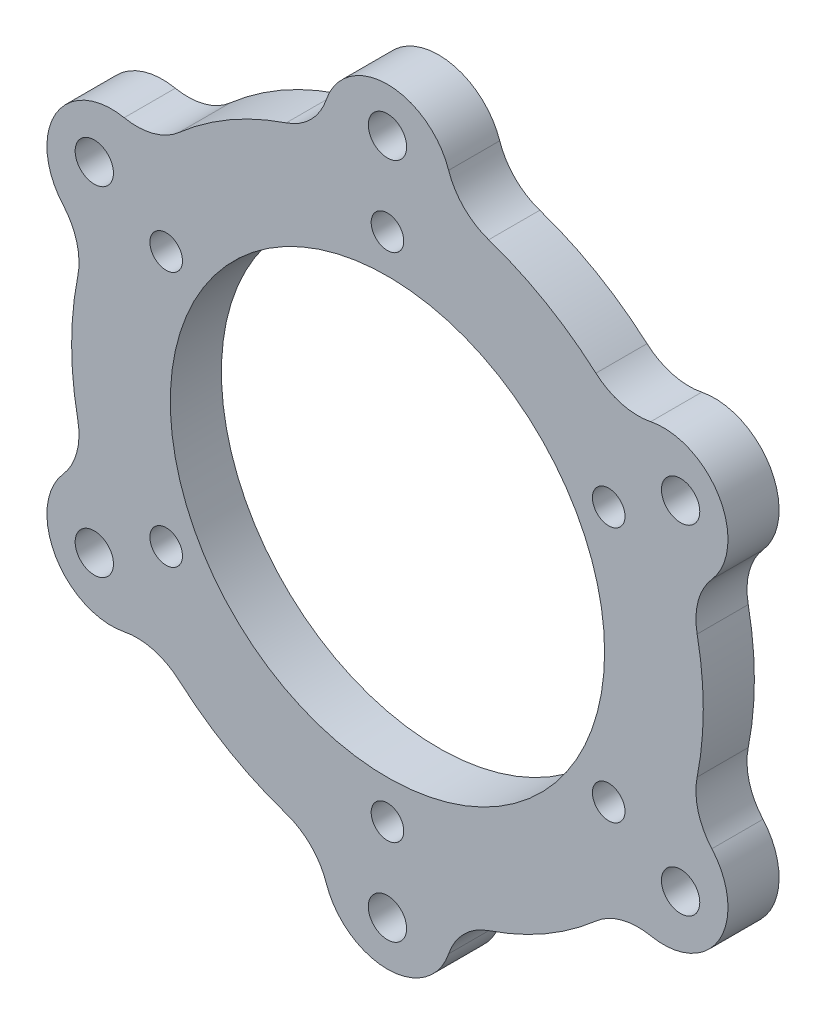
SolidWorks part; units mm, degrees
material "6063-T6"
ref_plane "Front Plane" through (0, 0, 0) normal (0, 0, 1) x (1, 0, 0)
ref_plane "Top Plane" through (0, 0, 0) normal (0, 1, 0) x (1, 0, 0)
ref_plane "Right Plane" through (0, 0, 0) normal (1, 0, 0) x (0, 0, -1)
sketch "Sketch5" plane through (0, 0, 0) normal (0, 1, 0) x (1, 0, 0)
  line L0 (0, -16.5008) -> (0, 15.0181) construction
ref_plane "Plane1" through (0, 0, 0) normal (-0.5, 0.866, 0) x (0, 0, -1)
sketch "Sketch2" plane through (0, 0, 0) normal (0, 0, 1) x (1, 0, 0)
  line L0 (0, 0) -> (0, 53) construction
  line L1 (0, 0) -> (0, 40) construction
  line L2 (0, 0) -> (0, 53) construction
  circle A0 centre (0, 0) radius 34
  circle A1 centre (0, 0) radius 60
  circle A2 centre (0, 53) radius 3
  circle A3 centre (45.8993, 26.5) radius 3
  circle A4 centre (45.8993, -26.5) radius 3
  circle A5 centre (0, -53) radius 3
  circle A6 centre (-45.8993, -26.5) radius 3
  circle A7 centre (-45.8993, 26.5) radius 3
  circle A11 centre (0, 0) radius 53 construction
  circle A12 centre (0, 40) radius 2.55
  circle A13 centre (34.641, 20) radius 2.55
  circle A14 centre (34.641, -20) radius 2.55
  circle A15 centre (0, -40) radius 2.55
  circle A16 centre (-34.641, -20) radius 2.55
  circle A17 centre (-34.641, 20) radius 2.55
  circle A18 centre (0, 0) radius 46.95 construction
  arc A19 (-15.849, 46.8413) -> (15.849, 46.8413) centre (0, 0) ccw
  arc A21 (-9.5776, 53.1206) -> (9.5776, 53.1206) centre (0, 49.8933) cw
  arc A22 (9.5776, 53.1206) -> (15.849, 46.8413) centre (19.0541, 56.3138) ccw
  circle A23 centre (0, 0) radius 49.45 construction
  arc A24 (-9.5776, 53.1206) -> (-15.849, 46.8413) centre (-19.0541, 56.3138) cw
  arc A25 (41.215, 34.8547) -> (50.7926, 18.2658) centre (43.2088, 24.9466) cw
  arc A26 (41.215, 34.8547) -> (32.6413, 37.1463) centre (39.2422, 44.6582) cw
  arc A27 (50.7926, 18.2658) -> (48.4903, 9.695) centre (58.2962, 11.6556) ccw
  arc A28 (50.7926, -18.2658) -> (41.215, -34.8547) centre (43.2088, -24.9466) cw
  arc A29 (50.7926, -18.2658) -> (48.4903, -9.695) centre (58.2962, -11.6556) cw
  arc A30 (41.215, -34.8547) -> (32.6413, -37.1463) centre (39.2422, -44.6582) ccw
  arc A31 (9.5776, -53.1206) -> (-9.5776, -53.1206) centre (0, -49.8933) cw
  arc A32 (9.5776, -53.1206) -> (15.849, -46.8413) centre (19.0541, -56.3138) cw
  arc A33 (-9.5776, -53.1206) -> (-15.849, -46.8413) centre (-19.0541, -56.3138) ccw
  arc A34 (-41.215, -34.8547) -> (-50.7926, -18.2658) centre (-43.2088, -24.9466) cw
  arc A35 (-41.215, -34.8547) -> (-32.6413, -37.1463) centre (-39.2422, -44.6582) cw
  arc A36 (-50.7926, -18.2658) -> (-48.4903, -9.695) centre (-58.2962, -11.6556) ccw
  arc A37 (-50.7926, 18.2658) -> (-41.215, 34.8547) centre (-43.2088, 24.9466) cw
  arc A38 (-50.7926, 18.2658) -> (-48.4903, 9.695) centre (-58.2962, 11.6556) cw
  arc A39 (-41.215, 34.8547) -> (-32.6413, 37.1463) centre (-39.2422, 44.6582) ccw
  point P24 (0, 0)
  point P42 (46.95, 0)
  point P43 (0, 0)
  point P46 (10, 48.4283)
  point P49 (-10, 48.4283)
  point P84 (0, 0)
  dimension "D1" = 6
  dimension "D2" = 68
  dimension "D3" = 120
  dimension "D9" = 5.1
  dimension "D7" = 93.9
  dimension "D12" = 10
  dimension "D10" = 40
  dimension "D4" = 0
  dimension "D11" = 20
  dimension "D8" = 2.5
  dimension "D5" = 6
  dimension "D6" = 6
  dimension "D13" = 6
extrude "Boss-Extrude1" add sketch "Sketch2" along normal blind 8 contours A21 A24 A19 A22 A0 A2 A12 A13 A14 A15 A16 A17 | A39 A37 A38 A19 A7 | A27 A25 A26 A19 A3 | A33 A31 A32 A19 A5 | A36 A34 A35 A19 A6 | A30 A28 A29 A19 A4 region at (52.9238, 23.9788, 0) region at (47.2282, -33.844, 0) region at (5.0355, 56.9038, 0) region at (-5.6959, -57.8232, 0) region at (-47.2282, 33.844, 0) region at (-52.9238, -23.9788, 0)
sketch "Sketch4" plane through (0, 0, 0) normal (-0.5, 0.866, 0) x (0, 0, -1)
  line L0 (0, 0) -> (-8, 0) construction
  line L3 (-16.5008, 0) -> (15.0181, 0) construction
  line L7 (0, -9.695) -> (0, 9.695)
  line L8 (0, 9.695) -> (-8, 9.695)
  line L9 (-8, 9.695) -> (-8, -9.695)
  line L10 (-8, -9.695) -> (0, -9.695)
  line L11 (0, -9.695) -> (0, 9.695)
  line L12 (0, 9.695) -> (-8, 9.695)
  line L13 (-8, 9.695) -> (-8, -9.695)
  line L14 (-8, -9.695) -> (0, -9.695)
  circle A4 centre (-4, 0) radius 2.1
  dimension "D1" = 0
  dimension "D2" = 4.2
equation "\"D7@Sketch2\"=88.900000+5mm"
